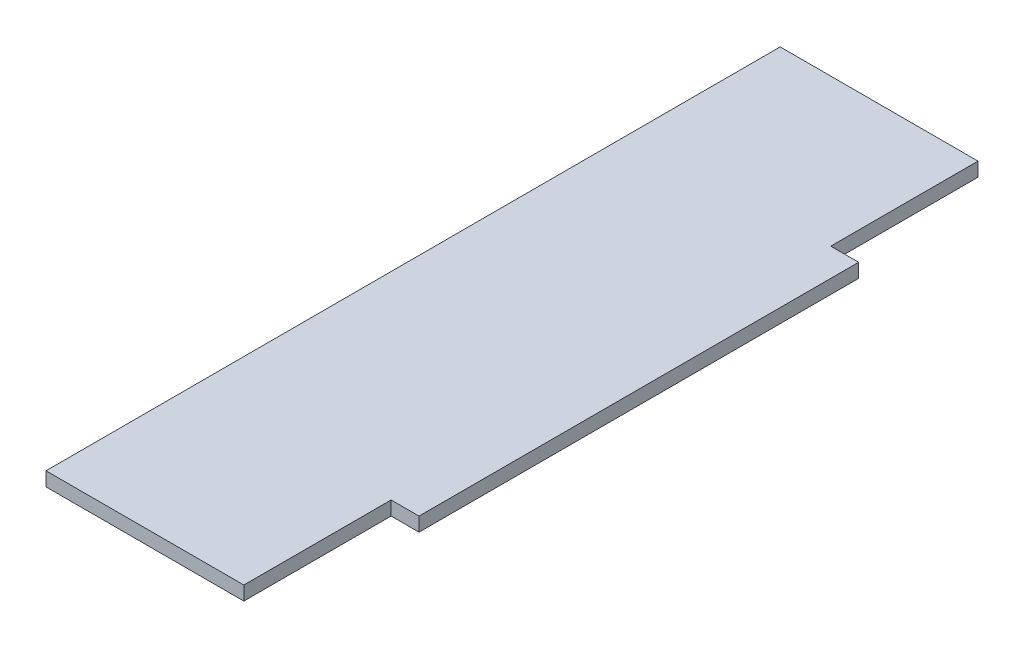
SolidWorks part; units mm, degrees
ref_plane "Front Plane" through (0, 0, 0) normal (0, 0, 1) x (1, 0, 0)
ref_plane "Top Plane" through (0, 0, 0) normal (0, 1, 0) x (1, 0, 0)
ref_plane "Right Plane" through (0, 0, 0) normal (1, 0, 0) x (0, 0, -1)
sketch "Sketch1" plane through (0, 0, 0) normal (0, 1, 0) x (1, 0, 0)
  line L0 (-22.5, 33.5) -> (22.5, 33.5)
  line L1 (22.5, 33.5) -> (22.5, 0)
  line L2 (22.5, 0) -> (28.85, 0)
  line L3 (28.85, 0) -> (28.85, -100)
  line L4 (28.85, -100) -> (22.5, -100)
  line L5 (22.5, -100) -> (22.5, -133.5)
  line L6 (22.5, -133.5) -> (-22.5, -133.5)
  line L7 (-22.5, -133.5) -> (-22.5, -100)
  line L8 (-22.5, -100) -> (-28.85, -100)
  line L9 (-28.85, -100) -> (-28.85, 0)
  line L10 (-28.85, 0) -> (-22.5, 0)
  line L11 (-22.5, 0) -> (-22.5, 33.5)
  line L12 (-22.5, 0) -> (-22.5, -100) construction
  point P11 (0, 33.5)
  point P14 (-28.85, -50)
  dimension "D1" = 6.35
  dimension "D2" = 100
  dimension "D3" = 45
  dimension "D4" = 167
extrude "Boss-Extrude1" add sketch "Sketch1" along normal blind 3.175 contours L11 L12 L7 L6 L5 L4 L3 L2 L1 L0 region at (2.0004, 0, 50)
equation "\"length\" = 167mm"
equation "\"w_mach\"= 45mm"
equation "\"w_tab\"= 100mm"
equation "\"t_wood\"= 0.125in"
equation "\"t_side\"= 0.25in"
equation "\"D1@Sketch1\"=\"t_side\""
equation "\"D2@Sketch1\"=\"w_tab\""
equation "\"D3@Sketch1\"=\"w_mach\""
equation "\"D4@Sketch1\"=\"length\""
equation "\"D1@Boss-Extrude1\"=\"t_wood\""
